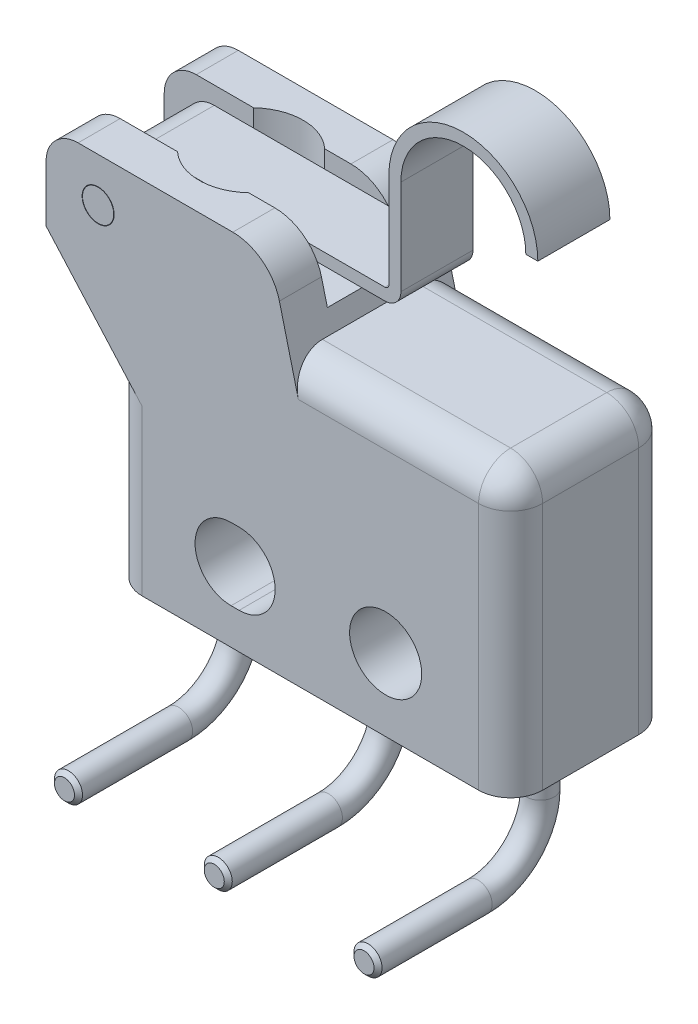
SolidWorks part; units mm, degrees
ref_plane "Front" through (0, 0, 0) normal (0, 0, 1) x (1, 0, 0)
ref_plane "Top" through (0, 0, 0) normal (0, 1, 0) x (1, 0, 0)
ref_plane "Right" through (0, 0, 0) normal (1, 0, 0) x (0, 0, -1)
sketch "Sketch4" plane through (0, 0, 0) normal (0, 0, 1) x (1, 0, 0)
  line L0 (0, 0) -> (12.7, 0)
  line L1 (12.7, 0) -> (12.7, 8.89)
  line L2 (12.7, 8.89) -> (5.715, 8.89)
  line L3 (5.715, 8.89) -> (5.08, 11.43)
  line L4 (5.08, 11.43) -> (-2.032, 11.43)
  line L5 (-2.032, 11.43) -> (-2.032, 8.636)
  line L6 (-2.032, 8.636) -> (0, 6.35)
  line L7 (0, 6.35) -> (0, 0)
  dimension "D1" = 12.7
  dimension "D2" = 8.89
  dimension "D3" = 11.43
  dimension "D4" = 14.732
  dimension "D5" = 6.35
  dimension "D6" = 8.636
  dimension "D7" = 6.985
  dimension "D8" = 7.62
extrude "Boss-Extrude3" add sketch "Sketch4" along normal blind 5.08
sketch "Sketch5" plane through (0, 0, 5.08) normal (0, 0, 1) x (1, 0, 0)
  line L0 (3.8354, 2.286) -> (4.0894, 2.286) construction
  line L1 (3.8354, 3.429) -> (4.0894, 3.429)
  line L2 (3.8354, 1.143) -> (4.0894, 1.143)
  line L3 (12.7, 0) -> (12.7, 8.89) construction
  line L4 (-2.032, 11.43) -> (-2.032, 8.636) construction
  circle A0 centre (8.7376, 2.286) radius 1.143
  arc A1 (3.8354, 3.429) -> (3.8354, 1.143) centre (3.8354, 2.286) ccw
  arc A2 (4.0894, 1.143) -> (4.0894, 3.429) centre (4.0894, 2.286) ccw
  circle A3 centre (-0.381, 10.033) radius 0.508
  point P4 (3.9624, 2.286)
  dimension "D1" = 2.286
  dimension "D2" = 4.7752
  dimension "D4" = 1.143
  dimension "D9" = 1.016
  dimension "D3" = 3.9624
  dimension "D5" = 0.254
  dimension "D6" = 2.286
  dimension "D7" = 7.747
  dimension "D8" = 1.651
extrude "Cut-Extrude1" cut sketch "Sketch5" against normal through all
sketch "Sketch6" plane through (0, 11.43, 0) normal (0, 1, 0) x (1, 0, 0)
  line L0 (-2.032, -1.3335) -> (0.8034, -1.3335)
  line L1 (-2.032, -5.08) -> (-2.032, 0) construction
  line L2 (5.842, -1.3335) -> (5.842, -3.7465)
  line L3 (5.842, -3.7465) -> (3.0574, -3.7465)
  line L4 (-2.032, -3.7465) -> (-2.032, -1.3335)
  line L5 (0.8034, -3.7465) -> (-2.032, -3.7465)
  line L6 (3.0574, -1.3335) -> (5.842, -1.3335)
  arc A0 (3.0574, -1.3335) -> (0.8034, -1.3335) centre (1.9304, -2.54) ccw
  arc A1 (0.8034, -3.7465) -> (3.0574, -3.7465) centre (1.9304, -2.54) ccw
  dimension "D6" = 3.302
  dimension "D1" = 1.3335
  dimension "D2" = 2.413
  dimension "D3" = 7.874
  dimension "D4" = 3.9624
  dimension "D5" = 1.2065
extrude "Cut-Extrude2" cut sketch "Sketch6" against normal blind 1.905
sketch "Sketch7" plane through (0, 9.525, 0) normal (0, 1, 0) x (1, 0, 0)
  line L0 (-2.032, -1.3335) -> (0, -1.3335)
  line L1 (0.8034, -1.3335) -> (-2.032, -1.3335) construction
  line L2 (0, -1.3335) -> (0, -3.7465)
  line L3 (-2.032, -3.7465) -> (0.8034, -3.7465) construction
  line L4 (0, -5.08) -> (0, 0) construction
  line L5 (0, -3.7465) -> (-2.032, -3.7465)
  line L6 (-2.032, -3.7465) -> (-2.032, -1.3335)
extrude "Cut-Extrude3" cut sketch "Sketch7" against normal through all
sketch "Sketch8" plane through (0, 0, 5.08) normal (0, 0, 1) x (1, 0, 0)
  circle A0 centre (-0.381, 10.033) radius 0.4953
  dimension "D1" = 0.9906
extrude "Boss-Extrude4" add sketch "Sketch8" against normal up to surface (5.08 mm away) up to face at (0.127, 10.033, 0)
sketch "Sketch9" plane through (0, 9.525, 0) normal (0, 1, 0) x (1, 0, 0)
  circle A0 centre (1.9304, -2.54) radius 1.5875
  dimension "D1" = 3.175
extrude "Boss-Extrude5" add sketch "Sketch9" along normal blind 0.254
sketch "Sketch10" plane through (0, 9.779, 0) normal (0, 1, 0) x (1, 0, 0)
  circle A0 centre (1.9304, -2.54) radius 0.7874
  dimension "D1" = 1.5748
extrude "Boss-Extrude6" add sketch "Sketch10" along normal blind 0.7112
ref_plane "Plane1" through (0, 0, 1.397) normal (0, 0, 1) x (1, 0, 0)
sketch "Sketch11" plane through (0, 0, 1.397) normal (0, 0, 1) x (1, 0, 0)
  line L0 (-0.381, 10.5537) -> (7.3152, 10.5537)
  line L1 (7.8232, 11.0617) -> (7.8232, 14.0716)
  line L2 (9.8044, 14.0716) -> (12.7054, 14.0716) construction
  line L3 (-0.381, 10.033) -> (-0.2079, 9.2826) construction
  line L4 (7.4422, 11.0617) -> (7.4422, 14.0716)
  line L5 (-0.381, 10.9347) -> (7.3152, 10.9347)
  line L6 (-0.264, 9.5256) -> (-0.1783, 9.1544)
  line L7 (11.7856, 14.0716) -> (12.1666, 14.0716)
  arc A0 (11.7856, 14.0716) -> (7.8232, 14.0716) centre (9.8044, 14.0716) ccw
  circle A1 centre (8.7376, 2.286) radius 1.143 construction
  arc A2 (7.8232, 11.0617) -> (7.3152, 10.5537) centre (7.3152, 11.0617) cw
  arc A3 (-0.381, 10.5537) -> (-0.264, 9.5256) centre (-0.381, 10.033) ccw
  arc A4 (12.1666, 14.0716) -> (7.4422, 14.0716) centre (9.8044, 14.0716) ccw
  arc A5 (7.4422, 11.0617) -> (7.3152, 10.9347) centre (7.3152, 11.0617) cw
  arc A6 (-0.381, 10.9347) -> (-0.1783, 9.1544) centre (-0.381, 10.033) ccw
  dimension "D1" = 1.0668
  dimension "D2" = 3.9624
  dimension "D3" = 0.508
  dimension "D4" = 1.0414
  dimension "D6" = 14.1478
  dimension "D5" = 0.381
extrude "Boss-Extrude7" add sketch "Sketch11" along normal blind 2.286 separate body
ref_plane "Plane2" through (6.35, 0, 0) normal (1, 0, 0) x (0, 0, -1)
ref_plane "Plane3" through (0, 0, 2.54) normal (0, 0, 1) x (1, 0, 0)
sketch "Sketch13" plane through (0, 0, 0) normal (0, -1, 0) x (1, 0, 0)
  line L0 (6.35, -50) -> (6.35, 50) construction
  line L1 (50, 2.54) -> (-50, 2.54) construction
  circle A0 centre (6.35, 2.54) radius 0.4445
  dimension "D1" = 0.889
ref_plane "Plane4" through (0, 0, 8.128) normal (0, 0, 1) x (1, 0, 0)
sketch "Sketch14" plane through (0, 0, 8.128) normal (0, 0, 1) x (1, 0, 0)
  line L0 (6.35, -50) -> (6.35, 50) construction
  line L1 (0, 0) -> (12.7, 0) construction
  circle A0 centre (6.35, -3.4925) radius 0.4445
  dimension "D1" = 0.889
  dimension "D2" = 3.937
sketch "Sketch15" plane through (6.35, 0, 0) normal (1, 0, 0) x (0, 0, -1)
  line L0 (-2.54, 0) -> (-2.54, -1.524)
  line L1 (-2.9845, 0) -> (-2.0955, 0) construction
  line L2 (-2.54, 50) -> (-2.54, -50) construction
  line L3 (-4.5085, -3.4925) -> (-8.128, -3.4925)
  line L4 (-8.128, 50) -> (-8.128, -50) construction
  arc A0 (-2.54, -1.524) -> (-4.5085, -3.4925) centre (-4.5085, -1.524) cw
  point P9 (-2.54, -3.4925)
  point P13 (0, 0)
  dimension "D1" = 1.9685
sweep "Sweep1" add profiles "Sketch13" path "Sketch15"
chamfer "Chamfer1" distance 0.127 angle 45 1 edges at (6.35, -3.937, 8.128)
pattern_linear "LPattern1" count 2 spacing 4.7498 along (1, 0, 0) count 2 spacing 4.7498 along (-1, 0, 0) of "Sweep1", "Chamfer1"
fillet "Fillet1" radius 1.016 9 edges at (9.2075, 8.89, 0) (9.2075, 8.89, 5.08) (12.7, 4.445, 0) (0, 3.175, 0) (0, 3.175, 5.08) (12.7, 4.445, 5.08) (-2.032, 11.43, 0.6667) (-2.032, 11.43, 4.4133) (12.7, 8.89, 2.54)
fillet "Fillet2" radius 1.524 2 edges at (5.08, 11.43, 0.6667) (5.08, 11.43, 4.4133)
sketch "Sketch16" plane through (0, 0, 0) normal (0, -1, 0) x (1, 0, 0)
  text T0 "<r90>C</r>" font "Century Gothic" height in points 5
extrude "Cut-Extrude4" cut sketch "Sketch16" against normal blind 0.0254
sketch "Sketch17" plane through (0, 0, 0) normal (0, -1, 0) x (1, 0, 0)
  text T0 "<r90>NC</r>" font "Century Gothic" height in points 5
extrude "Cut-Extrude5" cut sketch "Sketch17" against normal blind 0.0254
sketch "Sketch18" plane through (0, 0, 0) normal (0, -1, 0) x (1, 0, 0)
  text T0 "<r90>NO</r>" font "Century Gothic" height in points 5
extrude "Cut-Extrude6" cut sketch "Sketch18" against normal blind 0.0254
ref_axis "Axis1" through (1.6002, -3.4925, 4.5085) along (0, 0, 1)
ref_axis "Axis2" through (11.0998, -3.4925, 4.5085) along (0, 0, 1)
ref_point "Point1"
ref_point "Point2"
ref_axis "Axis3" through (1.6002, -1.524, 2.54) along (0, 1, 0)
ref_axis "Axis4" through (11.0998, -1.524, 2.54) along (0, 1, 0)
